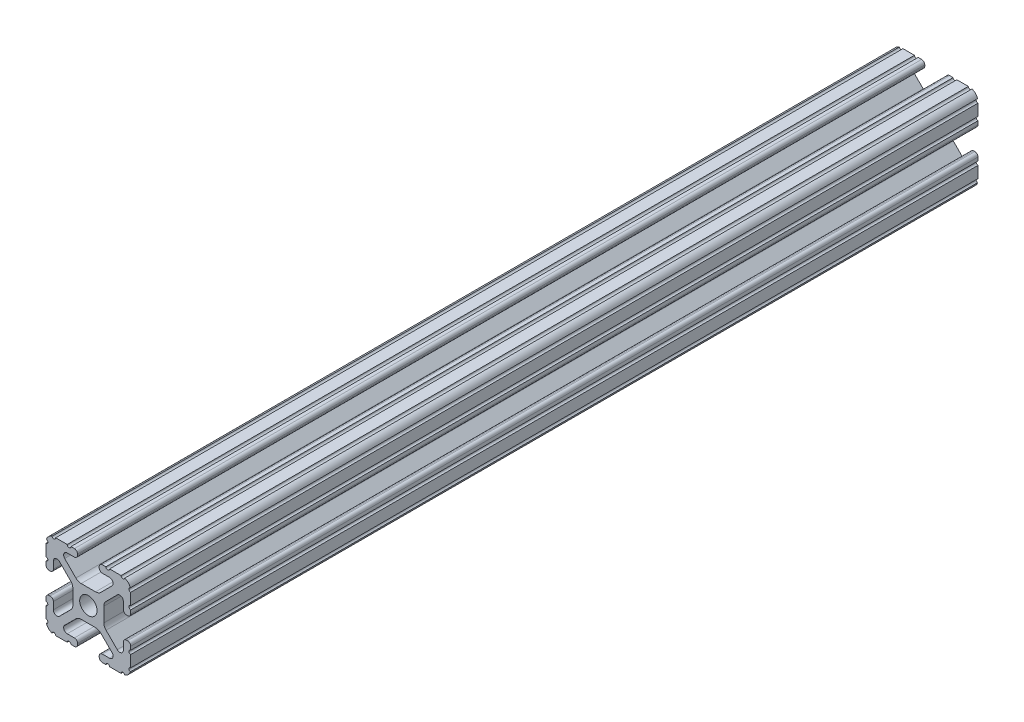
SolidWorks part; units mm, degrees
ref_plane "Front Plane" through (0, 0, 0) normal (0, 0, 1) x (1, 0, 0)
ref_plane "Top Plane" through (0, 0, 0) normal (0, 1, 0) x (1, 0, 0)
ref_plane "Right Plane" through (0, 0, 0) normal (1, 0, 0) x (0, 0, -1)
sketch "Sketch2" plane through (0, 0, 0) normal (0, 0, 1) x (1, 0, 0)
  line L0 (0, 12.7) -> (0, -12.7) construction
  line L1 (-12.7, 0) -> (12.7, 0) construction
  line L2 (3.2512, -12.7) -> (12.7, -12.7)
  line L3 (12.7, -12.7) -> (12.7, -3.2512)
  line L4 (3.2512, -12.7) -> (3.2512, -10.4902)
  line L5 (3.2512, -10.4902) -> (8.9276, -10.4902)
  line L6 (8.9276, -10.4902) -> (3.0856, -4.6482)
  line L7 (0, 0) -> (12.7, -12.7) construction
  line L8 (12.7, -3.2512) -> (10.4902, -3.2512)
  line L9 (10.4902, -3.2512) -> (10.4902, -8.9276)
  line L10 (10.4902, -8.9276) -> (4.6482, -3.0856)
  circle A0 centre (0, 0) radius 2.6035
  arc A1 (6.3485, -10.4902) -> (7.1039, -8.6665) centre (6.3485, -9.4219) ccw construction
  point P8 (0, -4.6482)
  dimension "Center Hole Diameter" = 5.207
  dimension "Rail Height" = 25.4
  dimension "Rail Width" = 25.4
  dimension "T-Slot Width" = 6.5024
  dimension "Slot Inner Width" = 14.8336
  dimension "Thickness" = 2.2098
  dimension "Slot Depth" = 5.842
  dimension "D1" = 2.2098
sketch "Sketch3" plane through (0, 0, 0) normal (1, 0, 0) x (0, 0, -1)
  line L0 (-152.4, -12.7) -> (152.4, -12.7) construction
  line L1 (-127, 0) -> (127, 0) construction
  dimension "Length" = 304.8
  dimension "D1" = 25.4
sketch "Sketch4" plane through (0, 0, 0) normal (0, 0, 1) x (1, 0, 0)
  line L0 (4.1904, -12.7) -> (10.1173, -12.7)
  line L1 (3.2512, -12.7) -> (12.7, -12.7) construction
  line L2 (3.2512, -12.7) -> (3.2512, -10.4902) construction
  line L3 (3.2512, -10.4902) -> (8.9276, -10.4902) construction
  line L4 (3.2512, -11.4294) -> (3.2512, -11.7608)
  line L5 (4.1904, -10.4902) -> (6.3485, -10.4902)
  line L6 (0, -4.6482) -> (2.164, -4.6482)
  line L7 (8.9276, -10.4902) -> (3.0856, -4.6482) construction
  line L8 (3.7373, -5.2999) -> (7.1039, -8.6665)
  line L9 (12.7, -12.7) -> (12.7, -3.2512) construction
  line L10 (10.4902, -8.9276) -> (4.6482, -3.0856) construction
  line L11 (10.4902, -3.2512) -> (10.4902, -8.9276) construction
  line L12 (10.4902, -6.3485) -> (10.4902, -4.1904)
  line L13 (12.7, -3.2512) -> (10.4902, -3.2512) construction
  line L14 (11.4294, -3.2512) -> (11.7608, -3.2512)
  line L15 (12.7, -4.1904) -> (12.7, -10.1173)
  line L16 (8.6665, -7.1039) -> (5.2999, -3.7373)
  line L17 (4.6482, 0) -> (4.6482, -2.164)
  line L18 (-12.7, 0) -> (12.7, 0) construction
  line L19 (0, -4.6482) -> (0, -2.6035)
  line L20 (0, 12.7) -> (0, -12.7) construction
  line L21 (4.6482, 0) -> (2.6035, 0)
  arc A0 (3.2512, -11.7608) -> (4.1904, -12.7) centre (4.1904, -11.7608) ccw
  arc A2 (3.2512, -11.4294) -> (4.1904, -10.4902) centre (4.1904, -11.4294) cw
  arc A3 (6.3485, -10.4902) -> (7.1039, -8.6665) centre (6.3485, -9.4219) ccw
  arc A4 (2.164, -4.6482) -> (3.7373, -5.2999) centre (2.164, -6.8732) cw
  arc A5 (10.1173, -12.7) -> (12.7, -10.1173) centre (10.1173, -10.1173) ccw
  arc A6 (8.6665, -7.1039) -> (10.4902, -6.3485) centre (9.4219, -6.3485) ccw
  arc A7 (10.4902, -4.1904) -> (11.4294, -3.2512) centre (11.4294, -4.1904) cw
  arc A8 (11.7608, -3.2512) -> (12.7, -4.1904) centre (11.7608, -4.1904) cw
  arc A9 (5.2999, -3.7373) -> (4.6482, -2.164) centre (6.8732, -2.164) cw
  circle A10 centre (0, 0) radius 2.6035 construction
  arc A11 (0, -2.6035) -> (2.6035, 0) centre (0, 0) ccw
  dimension "D1" = 2.5827
  dimension "D2" = 2.225
  dimension "D3" = 0.9392
extrude "Boss-Extrude1" add sketch "Sketch4" along normal mid plane 304.8
sketch "Sketch5" plane through (0, 0, 0) normal (0, 0, 1) x (1, 0, 0)
  line L0 (3.2512, -12.7) -> (12.7, -12.7) construction
  line L1 (4.1904, -10.4902) -> (6.3485, -10.4902) construction
  line L3 (0, 0) -> (12.7, -12.7) construction
  line L4 (6.3485, -10.4902) -> (6.3485, -12.7) construction
  line L5 (8.9276, -10.4902) -> (3.0856, -4.6482) construction
  circle A0 centre (10.3562, -12.7) radius 0.5524
  circle A1 centre (5.796, -12.7) radius 0.5524
  circle A2 centre (12.7, -10.3562) radius 0.5524
  circle A3 centre (12.7, -5.796) radius 0.5524
  point P10 (5.2694, -10.4902)
  point P12 (9.4219, -6.3485)
  dimension "D1" = 1.1049
extrude "Cut-Extrude1" cut sketch "Sketch5" against normal through all both and the other way through all
mirror "Mirror1" about plane through (0, 0, 0) normal (1, 0, 0) of bodies 137 134
mirror "Mirror2" about plane through (0, 0, 0) normal (0, 1, 0) of bodies 135
sketch "Sketch6" plane through (-4.6482, 0, 0) normal (-1, 0, 0) x (0, 0, 1)
  line L0 (-152.4, -2.164) -> (-152.4, 2.164) construction
  line L1 (-152.4, 0) -> (-95.3043, 0) construction
  circle A0 centre (-139.7, 0) radius 2.6035
  circle A1 centre (-63.5, 0) radius 2.6035
  point P10 (-139.7, 0)
  point P11 (-63.5, 0)
  point P12 (-139.7, 0)
  dimension "D1" = 5.207
  dimension "D3" = 5.207
  dimension "D2" = 12.7
  dimension "D4" = 76.2
extrude "Cut-Extrude2" cut sketch "Sketch6" against normal blind 38.1
sketch "Sketch7" plane through (-12.7, 0, 0) normal (-1, 0, 0) x (0, 0, 1)
  line L5 (152.4, -17.7226) -> (101.6, -17.7226)
  line L6 (152.4, -17.7226) -> (152.4, 33.134)
  line L7 (152.4, 33.134) -> (101.6, 33.134)
  line L8 (101.6, -17.7226) -> (101.6, 33.134)
  dimension "D1" = 50.8
  dimension "D2" = 50.8566
extrude "Cut-Extrude3" cut sketch "Sketch7" against normal blind 61.468 and the other way blind 61.468
equation "\"D1@Boss-Extrude1\"=\"Length@Sketch3\""
equation "\"D1@Sketch2\"=\"Thickness@Sketch2\""
equation "\"D2@Sketch4\"=\"Slot Inner Width@Sketch2\"*0.15"
equation "\"D1@Sketch4\"=\"D3@Sketch4\"*2.75"
equation "\"D3@Sketch4\"=\"Thickness@Sketch2\"*0.425"
equation "\"D1@Sketch5\"=\"Thickness@Sketch2\"*0.5"
